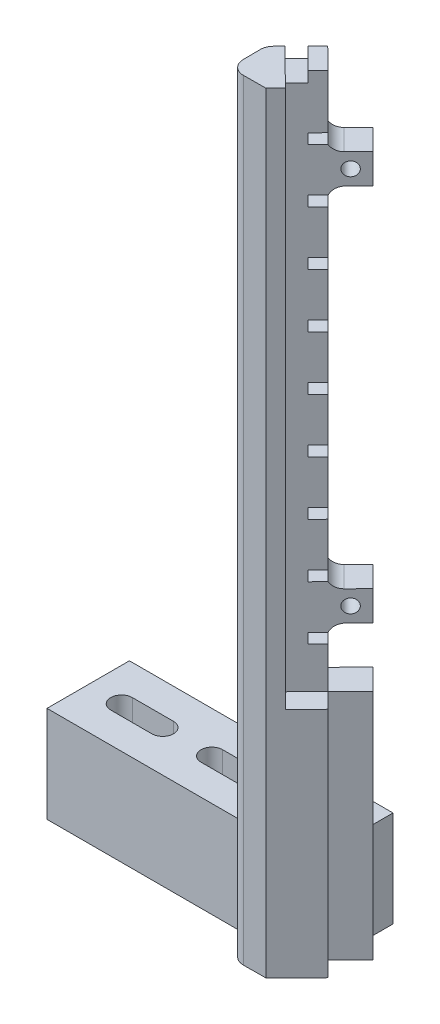
SolidWorks part; units mm, degrees
ref_plane "Front Plane" through (0, 0, 0) normal (0, 0, 1) x (1, 0, 0)
ref_plane "Top Plane" through (0, 0, 0) normal (0, 1, 0) x (1, 0, 0)
ref_plane "Right Plane" through (0, 0, 0) normal (1, 0, 0) x (0, 0, -1)
sketch "Sketch1" plane through (0, 0, 0) normal (0, 0, 1) x (1, 0, 0)
  line L0 (0, 0) -> (48.26, 0)
  line L6 (0, 0) -> (0, 17.78)
  line L10 (0, 17.78) -> (48.26, 17.78)
  line L11 (48.26, 0) -> (48.26, 17.78)
  dimension "D1" = 48.26
  dimension "D2" = 17.78
extrude "Boss-Extrude1" add sketch "Sketch1" against normal blind 15.24
sketch "Sketch3" plane through (0, 17.78, 0) normal (0, 1, 0) x (1, 0, 0)
  line L2 (52.4185, 15.24) -> (48.744, 11.5126)
  line L5 (48.2359, 10.9973) -> (52.4185, 15.24)
  line L9 (48.26, 15.24) -> (48.26, 11.0217)
  line L12 (48.26, 15.24) -> (0, 15.24) construction
  line L19 (0, 7.4477) -> (48.26, 7.62) construction
  line L20 (48.26, 15.24) -> (52.4185, 15.24)
  line L21 (48.744, 11.5126) -> (48.744, 15.24)
  line L22 (48.26, 15.24) -> (48.26, 0) construction
  line L25 (0, 15.24) -> (0, 0) construction
  line L26 (38.8873, 1.5142) -> (38.9315, -0.0668)
  line L30 (38.8873, 1.5142) -> (48.2359, 10.9973)
  line L31 (52.6607, 7.6514) -> (44.5872, -0.5382)
  line L32 (48.744, 11.5126) -> (52.6607, 7.6514)
  line L33 (47.4358, -3.3463) -> (44.5872, -0.5382)
  line L34 (45.6526, -5.1551) -> (47.4358, -3.3463)
  line L35 (38.9681, -5.2029) -> (45.6526, -5.1551)
  line L36 (38.9315, -0.0668) -> (38.9681, -5.2029)
  line L38 (51.3672, 0.6416) -> (47.4358, -3.3463)
  line L39 (48.5187, 3.4498) -> (51.3672, 0.6416)
  point P2 (0, 0)
  line M1 (0, 0) -> (48.26, 0)
  line M2 (48.26, 0) -> (48.26, 15.24)
  dimension "D1" = 11.5
sketch "Sketch4" plane through (0, 17.78, 0) normal (0, 1, 0) x (1, 0, 0)
  line L0 (30.48, 7.62) -> (22.86, 7.62) construction
  line L1 (30.48, 5.62) -> (22.86, 5.62)
  line L2 (30.48, 9.62) -> (22.86, 9.62)
  line L3 (13.78, 7.62) -> (6.16, 7.62) construction
  line L4 (13.78, 5.62) -> (6.16, 5.62)
  line L5 (13.78, 9.62) -> (6.16, 9.62)
  line L6 (48.26, 0) -> (0, 0) construction
  line L7 (48.26, 15.24) -> (48.26, 0) construction
  arc A0 (30.48, 5.62) -> (30.48, 9.62) centre (30.48, 7.62) ccw
  arc A1 (22.86, 9.62) -> (22.86, 5.62) centre (22.86, 7.62) ccw
  arc A2 (13.78, 5.62) -> (13.78, 9.62) centre (13.78, 7.62) ccw
  arc A3 (6.16, 9.62) -> (6.16, 5.62) centre (6.16, 7.62) ccw
  point P2 (26.67, 7.62)
  point P7 (9.97, 7.62)
  point P14 (32.48, 7.62)
  point P16 (4.16, 7.62)
  point P18 (15.78, 7.62)
  point P19 (20.86, 7.62)
  dimension "D1" = 4
  dimension "D2" = 17.78
  dimension "D3" = 7.62
  dimension "D4" = 7.62
  dimension "D5" = 5.08
extrude "Cut-Extrude2" cut sketch "Sketch4" against normal through all
ref_plane "Plane2" through (0, 0, -7.62) normal (0, 0, 1) x (1, 0, 0)
extrude "Boss-Extrude7" add sketch "Sketch3" along normal blind 124.72 contours L26 L36 L35 M1 | L32 L2 L5 L31 M2 | L19 L30 L26 L31 M1 M2 | L30 L19 L5 M2 region at (49.7429, 17.78, -7.5618) region at (47.1382, 17.78, -8.7499) region at (44.2223, 17.78, -3.4177) region at (42.5565, 17.78, 2.7065)
extrude "Boss-Extrude10" add sketch "Sketch3<15>" against normal through all contours L20 L5 M2 | L32 L2 L5 L31 M2 | L26 L36 L35 L34 L33 L31 M1 | L39 L31 L33 L38 M2 M1 region at (49.7429, 17.78, -7.5618) region at (48.497, 17.78, -13.2511) region at (48.1974, 17.78, 0.2393) region at (42.5565, 17.78, 2.7065)
sketch "Sketch3<15>" plane through (0, 17.78, 0) normal (0, 1, 0) x (1, 0, 0) same geometry as "Sketch3"
ref_plane "Plane3" through (22.881, 0, 22.5566) normal (0.7121, 0, 0.702) x (0.702, 0, -0.7121)
extrude "Boss-Extrude11" add sketch "Sketch3<16>" along normal blind 25.22 contours L39 L31 L33 L38 M2 M1 | L31 M2 M1 region at (47.2126, 17.78, -1.0625) region at (48.1974, 17.78, 0.2393)
sketch "Sketch3<16>" plane through (0, 17.78, 0) normal (0, 1, 0) x (1, 0, 0) same geometry as "Sketch3"
hole_wizard "Tapped Hole for M2.5x0.45 Helicoil1" positions "Sketch6" profile "Sketch8" tap size "M2.5x0.45" standard "Helicoil® Metric" end condition up to next
sketch "Sketch6" plane through (72.1766, -14.555, -27.448) normal (0.7121, 0, 0.702) x (0.702, 0, -0.7121)
  line L4 (-39.2988, 157.055) -> (-39.2988, 57.555) construction
  line L8 (-33.6988, 57.555) -> (-39.2988, 57.555) construction
  point P0 (-30.7488, 71.255)
  point P7 (-30.7488, 141.2549)
  dimension "D1" = 13.7
  dimension "D2" = 8.55
  dimension "D3" = 69.9999
sketch "Sketch8" plane through (50.5897, 56.7, -5.5506) normal (0, 1, 0) x (0.702, 0, -0.7121)
  line L0 (0, 0) -> (0, 5.5)
  line L1 (0, 5.5) -> (1.275, 5.5)
  line L2 (1.275, 5.5) -> (1.275, 0)
  line L5 (1.275, 0) -> (0, 0)
  line L11 (0, -6.35) -> (0, 107.95) construction
  dimension "Thru Tap Drill Dia." = 2.55
  dimension "Thru Tap Drill Depth" = 5.5
cosmetic thread "Hole Thread5" parameters "D1"=3.7998, "D2"=3.55
cosmetic thread "Hole Thread6" parameters "D1"=3.7998, "D2"=3.55
sketch "Sketch10" plane through (22.881, 0, 22.5566) normal (0.7121, 0, 0.702) x (0.702, 0, -0.7121)
  line L3 (33.9188, 140.5) -> (30.9188, 140.5)
  line L13 (30.9188, 140.5) -> (30.9188, 99.5492)
  line L46 (33.9188, 43) -> (30.9188, 43)
  line L47 (30.9188, 43) -> (30.9188, 99.5492)
  line L48 (30.9188, 142.5) -> (30.9188, 43) construction
  line L49 (36.5188, 43) -> (33.9188, 43)
  line L50 (30.9188, 142.5) -> (30.9188, 43) construction
  line L51 (36.5188, 43) -> (30.9188, 43) construction
  line L53 (36.5188, 50.6) -> (36.5188, 43)
  line L54 (36.5188, 50.6) -> (33.9188, 50.6)
  line L55 (33.9188, 50.6) -> (33.9188, 52.5)
  line L56 (33.9188, 52.5) -> (36.5188, 52.5)
  line L57 (42.4188, 53.95) -> (38.7876, 53.95)
  line L58 (42.4188, 53.95) -> (42.4188, 59.45)
  line L59 (42.4188, 59.45) -> (38.623, 59.45)
  line L60 (36.5188, 60.6) -> (33.9188, 60.6)
  line L61 (33.9188, 60.6) -> (33.9188, 62.5)
  line L62 (33.9188, 62.5) -> (36.5188, 62.5)
  line L63 (33.9188, 82.5) -> (36.5188, 82.5)
  line L64 (33.9188, 80.6) -> (33.9188, 82.5)
  line L65 (36.5188, 80.6) -> (33.9188, 80.6)
  line L66 (36.5188, 80.6) -> (36.5188, 72.5)
  line L67 (33.9188, 70.6) -> (33.9188, 72.5)
  line L68 (33.9188, 72.5) -> (36.5188, 72.5)
  line L69 (36.5188, 70.6) -> (33.9188, 70.6)
  line L70 (36.5188, 70.6) -> (36.5188, 62.5)
  line L71 (33.9188, 110.6) -> (33.9188, 112.5)
  line L72 (36.5188, 110.6) -> (33.9188, 110.6)
  line L73 (36.5188, 110.6) -> (36.5188, 102.5)
  line L74 (33.9188, 102.5) -> (36.5188, 102.5)
  line L75 (33.9188, 100.6) -> (33.9188, 102.5)
  line L76 (36.5188, 100.6) -> (33.9188, 100.6)
  line L77 (36.5188, 100.6) -> (36.5188, 92.5)
  line L78 (33.9188, 92.5) -> (36.5188, 92.5)
  line L79 (33.9188, 90.6) -> (33.9188, 92.5)
  line L80 (36.5188, 90.6) -> (33.9188, 90.6)
  line L81 (36.5188, 90.6) -> (36.5188, 82.5)
  line L82 (36.5188, 142.5) -> (33.9188, 142.5)
  line L83 (33.9188, 140.5) -> (33.9188, 142.5)
  line L84 (33.9188, 132.5) -> (36.5188, 132.5)
  line L85 (36.5188, 142.5) -> (36.5188, 132.5)
  line L86 (33.9188, 130.6) -> (33.9188, 132.5)
  line L87 (36.5188, 130.6) -> (33.9188, 130.6)
  line L88 (42.4188, 129.45) -> (38.623, 129.45)
  line L89 (42.4188, 123.95) -> (42.4188, 129.45)
  line L90 (42.4188, 123.95) -> (38.7876, 123.95)
  line L91 (33.9188, 122.5) -> (36.5188, 122.5)
  line L92 (33.9188, 120.6) -> (33.9188, 122.5)
  line L93 (36.5188, 120.6) -> (33.9188, 120.6)
  line L94 (36.5188, 120.6) -> (36.5188, 112.5)
  line L95 (33.9188, 112.5) -> (36.5188, 112.5)
  line L96 (36.5188, 142.5) -> (42.4188, 142.5)
  line L97 (42.4188, 142.5) -> (42.4188, 129.45)
  line L98 (42.4188, 123.95) -> (42.4188, 59.45)
  line L99 (36.5188, 43) -> (42.4188, 43)
  line L100 (42.4188, 142.5) -> (42.4188, 0) construction
  line L101 (42.4188, 43) -> (42.4188, 53.95)
  line L102 (33.9188, 142.5) -> (30.9188, 142.5)
  line L103 (30.9188, 142.5) -> (30.9188, 140.5)
  arc A4 (36.5188, 52.5) -> (38.7876, 53.95) centre (38.7876, 51.45) cw
  arc A5 (38.623, 59.45) -> (36.5188, 60.6) centre (38.623, 61.95) cw
  arc A6 (38.623, 129.45) -> (36.5188, 130.6) centre (38.623, 131.95) cw
  arc A7 (36.5188, 122.5) -> (38.7876, 123.95) centre (38.7876, 121.45) cw
extrude "Cut-Extrude3" cut sketch "Sketch10" against normal through all contours A4 L56 L55 L54 L53 L99 L101 L57 | A7 L91 L92 L93 L94 L95 L71 L72 L73 L74 L75 L76 L77 L78 L79 L80 L81 L63 L64 L65 L66 L68 L67 L69 L70 L62 L61 L60 A5 L59 L98 L90 | A6 L88 L97 L96 L85 L84 L86 L87 | L102 L103 L3 L83 region at (45.6403, 141.5, -0.53) region at (50.4233, 135.7604, -5.3819) region at (50.3978, 48.6278, -5.356) region at (50.347, 91.6712, -5.3044)
fillet "Fillet1" radius 2.54 1 edges at (38.9681, 71.25, 5.2029)
fillet "Fillet2" radius 2.54 1 edges at (38.8873, 80.14, -1.5142)
